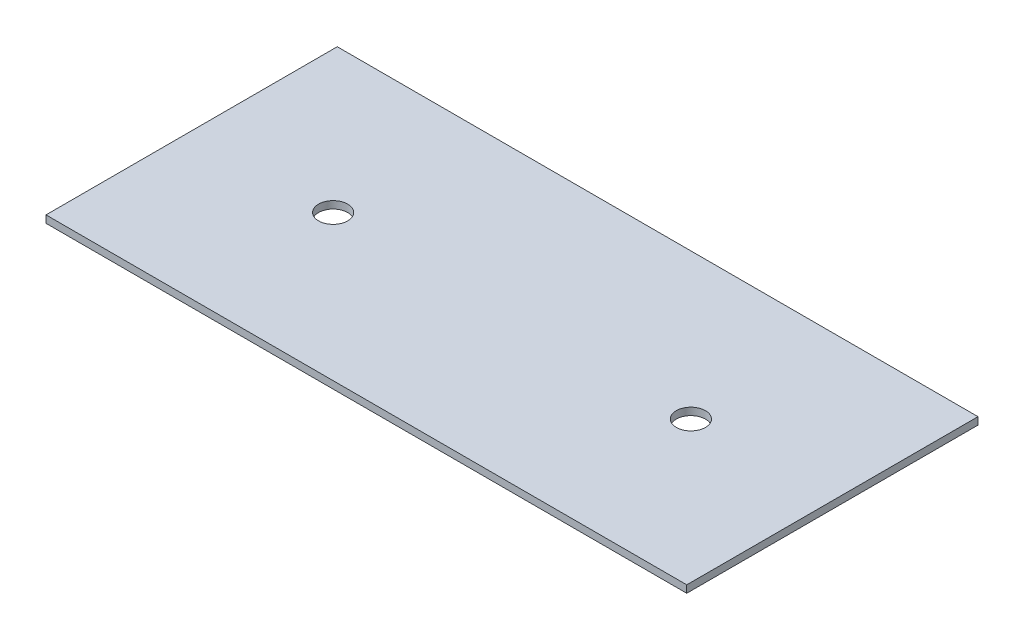
SolidWorks part; units mm, degrees
material "6061 Alloy"
ref_plane "Front Plane" through (0, 0, 0) normal (0, 0, 1) x (1, 0, 0)
ref_plane "Top Plane" through (0, 0, 0) normal (0, 1, 0) x (1, 0, 0)
ref_plane "Right Plane" through (0, 0, 0) normal (1, 0, 0) x (0, 0, -1)
sketch "Sketch1" plane through (0, 0, 0) normal (0, 1, 0) x (1, 0, 0)
  line L0 (-39, 0) -> (39, 0) construction
  line L2 (-69.85, -31.75) -> (69.85, -31.75)
  line L3 (-69.85, -31.75) -> (-69.85, 31.75)
  line L4 (-69.85, 31.75) -> (69.85, 31.75)
  line L5 (69.85, -31.75) -> (69.85, 31.75)
  line L6 (-69.85, -31.75) -> (69.85, 31.75) construction
  line L7 (-69.85, 31.75) -> (69.85, -31.75) construction
  circle A0 centre (39, 0) radius 3.175
  circle A1 centre (-39, 0) radius 3.175
  point P3 (0, 0)
  dimension "D2" = 6.35
  dimension "D1" = 78
  dimension "D3" = 63.5
  dimension "D4" = 139.7
extrude "Boss-Extrude1" add sketch "Sketch1" along normal blind 1.6
